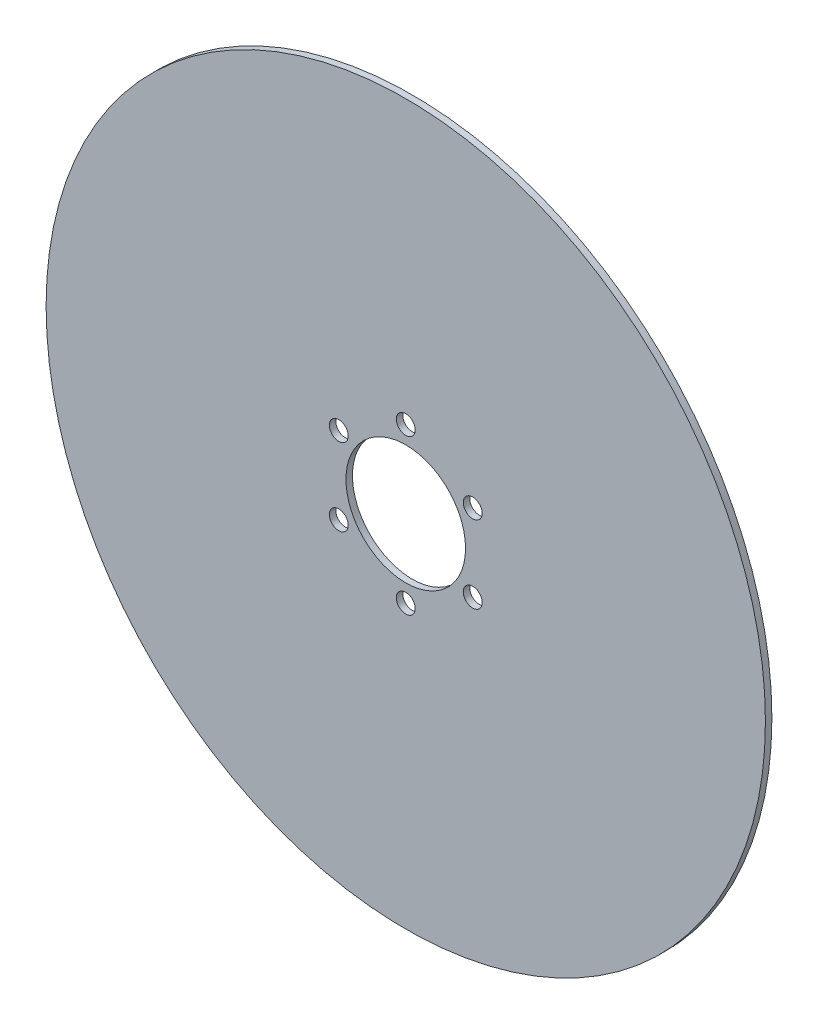
SolidWorks part; units mm, degrees
ref_plane "Front Plane" through (0, 0, 0) normal (0, 0, 1) x (1, 0, 0)
ref_plane "Top Plane" through (0, 0, 0) normal (0, 1, 0) x (1, 0, 0)
ref_plane "Right Plane" through (0, 0, 0) normal (1, 0, 0) x (0, 0, -1)
sketch "Sketch1" plane through (0, 0, 0) normal (0, 0, 1) x (1, 0, 0)
  circle A0 centre (0, 0) radius 100
  circle A1 centre (0, 0) radius 16.625
  circle A2 centre (0, 0) radius 21.5 construction
  circle A3 centre (0, 21.5) radius 2.625
  circle A4 centre (18.6195, 10.75) radius 2.625
  circle A5 centre (18.6195, -10.75) radius 2.625
  circle A6 centre (0, -21.5) radius 2.625
  circle A7 centre (-18.6195, -10.75) radius 2.625
  circle A8 centre (-18.6195, 10.75) radius 2.625
  point P19 (0, 0)
  dimension "D1" = 200
  dimension "D2" = 33.25
  dimension "D3" = 43
  dimension "D4" = 5.25
  dimension "D5" = 6
extrude "Boss-Extrude1" add sketch "Sketch1" along normal blind 0.9 and the other way blind 0.9
